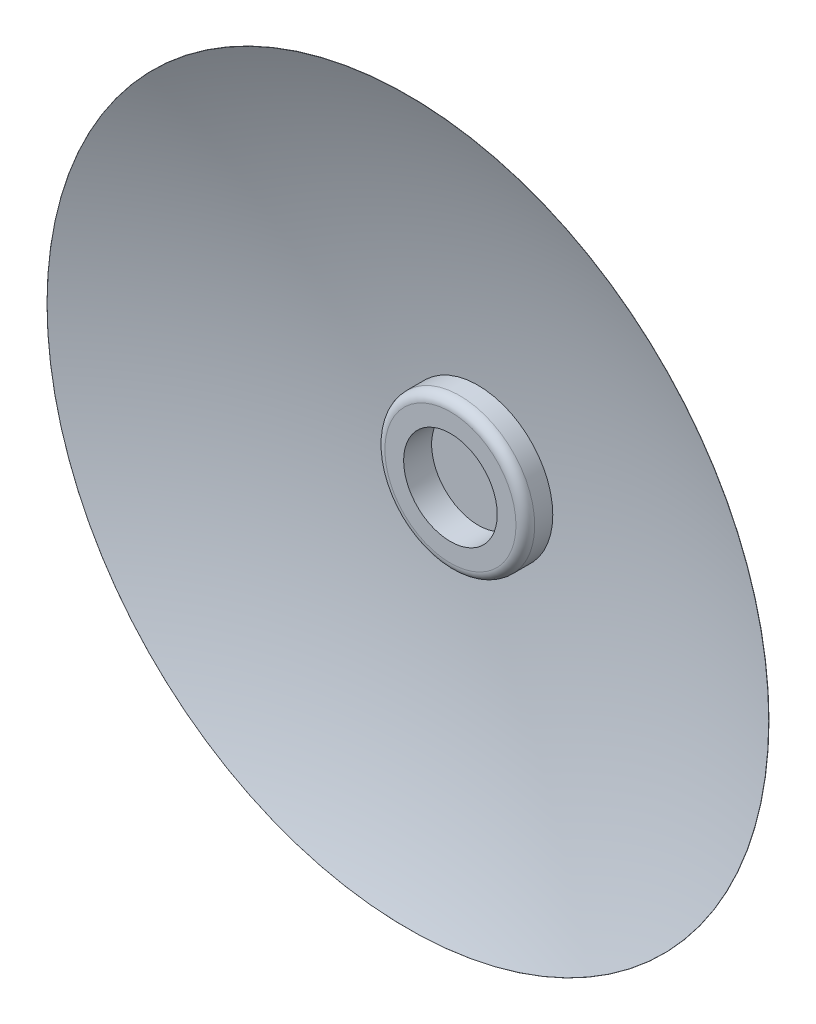
SolidWorks part; units mm, degrees
note: The reader was unsure of these and kept them because the rebuilt part matched: shared geometry of "Sketch2<4>".
ref_plane "Front Plane" through (0, 0, 0) normal (0, 0, 1) x (1, 0, 0)
ref_plane "Top Plane" through (0, 0, 0) normal (0, 1, 0) x (1, 0, 0)
ref_plane "Right Plane" through (0, 0, 0) normal (1, 0, 0) x (0, 0, -1)
sketch "Sketch2" plane through (0, 0, 0) normal (1, 0, 0) x (0, 0, -1)
  line L0 (0, 0) -> (398, 0)
  line L1 (0, 0) -> (0, 10)
  line L2 (0, 10) -> (383, 10)
  line L3 (375, 10) -> (375, 385.4448) construction
  line L4 (383, 10) -> (383, 385.4448) construction
  line L5 (373.0973, 80) -> (353.0973, 80)
  line L6 (343.0973, 70) -> (343.0973, 10)
  line L7 (383, 10) -> (398, 10)
  line L8 (398, 0) -> (398, 10)
  line L9 (0, 35) -> (398, 35)
  line L10 (0, 10) -> (48, 10)
  line L11 (48, 10) -> (48, 0)
  line L12 (48, 0) -> (0, 0)
  line L13 (0, 35) -> (48, 35)
  arc A0 (375, 10) -> (297.6803, 385.4053) centre (-575, 10) ccw
  arc A1 (297.8624, 385.4879) -> (383, 10) centre (-487.588, 10) cw
  arc A2 (297.6803, 385.4053) -> (297.8624, 385.4879) centre (297.7721, 385.4448) cw
  arc A3 (375, 10) -> (373.6791, 60.0791) centre (-575, 10) ccw
  arc A4 (370.6971, 60.2177) -> (360, 10) centre (-25.0674, 118.2731) cw
  arc A5 (370.6971, 60.2177) -> (373.6791, 60.0791) centre (372.1812, 60) cw
  arc A6 (379.3292, 89.8624) -> (383, 10) centre (-487.588, 10) cw
  arc A7 (382.2674, 90.4042) -> (398, 10) centre (-113.6805, -48.3786) cw
  arc A8 (382.2674, 90.4042) -> (379.3292, 89.8624) centre (380.8229, 90) ccw
  arc A9 (353.0973, 80) -> (343.0973, 70) centre (353.0973, 70) ccw
  point P13 (295.6894, 390)
  point P34 (343.0973, 80)
  dimension "D3" = 950
  dimension "D6" = 0.1
  dimension "D8" = 1.5
  dimension "D9" = 400
  dimension "D14" = 1.5
  dimension "D16" = 515
  dimension "D18" = 10
  dimension "D1" = 380
  dimension "D2" = 10
  dimension "D4" = 575
  dimension "D5" = 8
  dimension "D7" = 15
  dimension "D10" = 50
  dimension "D11" = 30
  dimension "D12" = 80
  dimension "D13" = 15
  dimension "D15" = 80
  dimension "D17" = 35
  dimension "D19" = 350
revolve "Revolve1" add sketch "Sketch2" angle 360 about L0
revolve "Revolve4" add sketch "Sketch2<4>" angle 360 about L0
sketch "Sketch2<4>" plane through (0, 0, 0) normal (1, 0, 0) x (0, 0, -1) same geometry as "Sketch2"
scale "Scale2" scale about centroid uniform scaling yes scale factor 0.2
sketch "Sketch3" plane through (0, 0, -287.8312) normal (0, 0, 1) x (1, 0, 0)
  circle A0 centre (0, 0) radius 10
  dimension "D1" = 20
extrude "Cut-Extrude1" cut sketch "Sketch3" against normal blind 65
